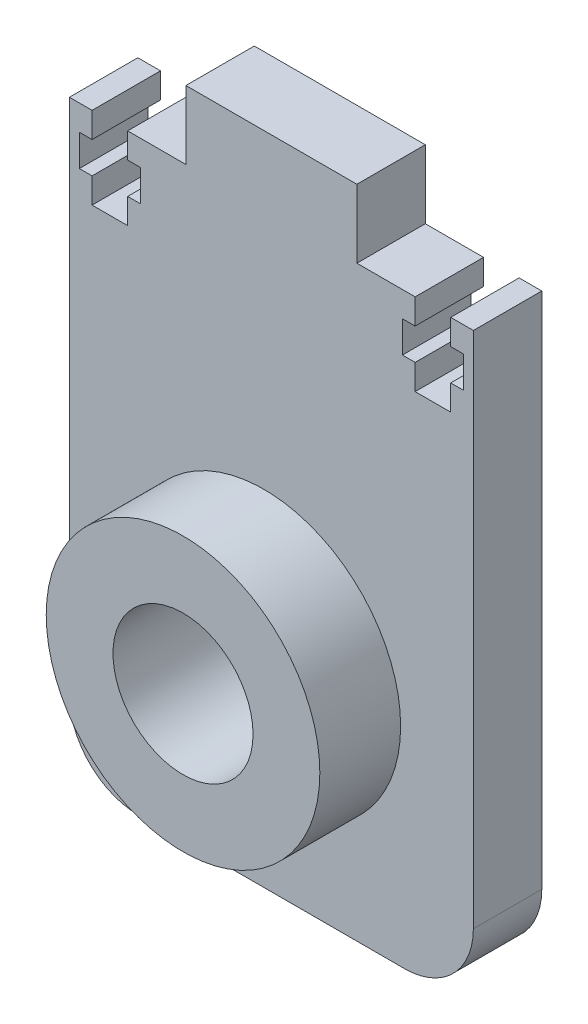
SolidWorks part; units mm, degrees
ref_plane "Front Plane" through (0, 0, 0) normal (0, 0, 1) x (1, 0, 0)
ref_plane "Top Plane" through (0, 0, 0) normal (0, 1, 0) x (1, 0, 0)
ref_plane "Right Plane" through (0, 0, 0) normal (1, 0, 0) x (0, 0, -1)
sketch "Sketch12" plane through (0, 0, 0) normal (0, 0, 1) x (1, 0, 0)
  line L0 (62.1258, 0) -> (62.1258, 121.71)
  line L1 (62.1258, 121.71) -> (137.1258, 121.71)
  line L2 (62.1258, 0) -> (137.1258, 0)
  line L3 (137.1258, 121.71) -> (137.1258, 0)
  line L4 (99.6258, 38.628) -> (99.6258, 121.71) construction
  circle A0 centre (99.6258, 38.628) radius 25.4
  circle A1 centre (99.6258, 38.628) radius 6.5
  dimension "D3" = 50.8
  dimension "D4" = 13
  dimension "D1" = 121.71
  dimension "D2" = 75
  dimension "D5" = 83.082
extrude "Boss-Extrude10" add sketch "Sketch12" along normal blind 12.7 separate body contours L1 L3 L2 L0
sketch "Sketch15" plane through (0, 0, 12.7) normal (0, 0, 1) x (1, 0, 0)
  circle A0 centre (98.2196, 38.6276) radius 25.4
  dimension "D1" = 50.8
extrude "Boss-Extrude11" add sketch "Sketch15" along normal blind 15
sketch "Sketch23" plane through (0, 0, 27.7) normal (0, 0, 1) x (1, 0, 0)
  circle A0 centre (98.2196, 38.6276) radius 13
  dimension "D1" = 26
extrude "Cut-Extrude7" cut sketch "Sketch23" against normal through all
fillet "Fillet2" radius 12.8 2 edges at (137.1258, 0, 6.35) (62.1258, 0, 6.35)
sketch "Sketch25" plane through (0, 0, 12.7) normal (0, 0, 1) x (1, 0, 0)
  line L0 (137.1258, 121.71) -> (137.1258, 109.01)
  line L1 (137.1258, 121.71) -> (137.1258, 12.8) construction
  line L2 (99.6258, 121.71) -> (99.6258, 98.7556)
  line L3 (62.1258, 12.8) -> (62.1258, 121.71) construction
  line L4 (62.1258, 109.01) -> (62.1258, 121.71)
  line L5 (115.5008, 109.01) -> (115.5008, 121.71)
  line L6 (62.1258, 121.71) -> (137.1258, 121.71) construction
  line L7 (115.5008, 121.71) -> (83.7508, 121.71)
  line L8 (83.7508, 121.71) -> (83.7508, 109.01)
  line L9 (83.7508, 109.01) -> (99.6258, 109.01)
  line L10 (99.6258, 109.01) -> (115.5008, 109.01)
  line L11 (137.1258, 109.01) -> (115.5008, 109.01)
  line L12 (115.5008, 121.71) -> (83.7508, 121.71)
  line L13 (83.7508, 109.01) -> (62.1258, 109.01)
  line M10 (137.1258, 12.8) -> (137.1258, 121.71)
  line M11 (137.1258, 121.71) -> (62.1258, 121.71)
  line M12 (62.1258, 121.71) -> (62.1258, 12.8)
  dimension "D1" = 12.7
  dimension "D2" = 31.75
extrude "Cut-Extrude9" cut sketch "Sketch25" against normal through all contours L13 L8 M11 M12 | L11 L5 M10 M11 region at (126.3133, 115.36, 12.7) region at (72.9383, 115.36, 12.7)
sketch "Sketch27" plane through (0, 0, 12.7) normal (0, 0, 1) x (1, 0, 0)
  line L0 (132.9173, 109.01) -> (132.9173, 104.311)
  line L1 (137.1258, 109.01) -> (115.5008, 109.01) construction
  line L2 (132.9173, 104.311) -> (135.2793, 104.311)
  line L3 (135.2793, 104.311) -> (135.2793, 98.469)
  line L4 (135.2793, 98.469) -> (132.9173, 98.469)
  line L5 (132.9173, 98.469) -> (132.9173, 93.77)
  line L6 (132.9173, 93.77) -> (126.3133, 93.77)
  line L7 (126.3133, 93.77) -> (126.3133, 98.469)
  line L8 (126.3133, 98.469) -> (123.9513, 98.469)
  line L9 (123.9513, 98.469) -> (123.9513, 104.311)
  line L10 (123.9513, 104.311) -> (126.3133, 104.311)
  line L11 (126.3133, 104.311) -> (126.3133, 109.01)
  line L12 (99.6258, 121.71) -> (99.6258, 67.6415) construction
  line L13 (83.7508, 121.71) -> (115.5008, 121.71) construction
  line L14 (72.9383, 98.469) -> (75.3003, 98.469)
  line L15 (75.3003, 98.469) -> (75.3003, 104.311)
  line L16 (75.3003, 104.311) -> (72.9383, 104.311)
  line L17 (72.9383, 104.311) -> (72.9383, 109.01)
  line L18 (66.3343, 109.01) -> (66.3343, 104.311)
  line L19 (66.3343, 104.311) -> (63.9723, 104.311)
  line L20 (63.9723, 104.311) -> (63.9723, 98.469)
  line L21 (63.9723, 98.469) -> (66.3343, 98.469)
  line L22 (66.3343, 98.469) -> (66.3343, 93.77)
  line L23 (66.3343, 93.77) -> (72.9383, 93.77)
  line L24 (72.9383, 93.77) -> (72.9383, 98.469)
  line L25 (132.9173, 109.01) -> (126.3133, 109.01)
  line L26 (72.9383, 109.01) -> (66.3343, 109.01)
  dimension "D1" = 6.604
  dimension "D2" = 11.328
  dimension "D3" = 15.24
  dimension "D4" = 5.842
ref_axis "Axis1" through (99.6258, 121.71, 12.7) along (0, -1, 0)
extrude "Cut-Extrude10" cut sketch "Sketch27" against normal through all
